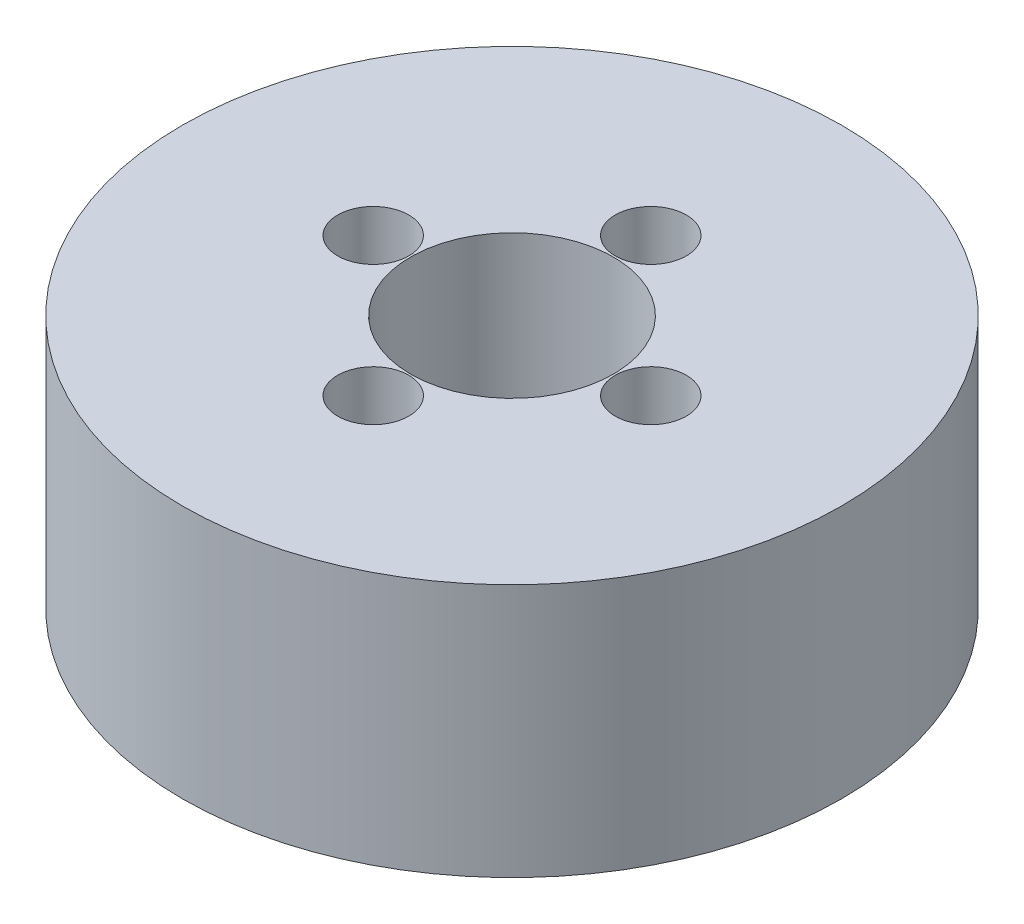
SolidWorks part; units mm, degrees
ref_plane "Front Plane" through (0, 0, 0) normal (0, 0, 1) x (1, 0, 0)
ref_plane "Top Plane" through (0, 0, 0) normal (0, 1, 0) x (1, 0, 0)
ref_plane "Right Plane" through (0, 0, 0) normal (1, 0, 0) x (0, 0, -1)
sketch "Sketch1" plane through (0, 0, 0) normal (0, 1, 0) x (1, 0, 0)
  circle A0 centre (0, 0) radius 32.5
  dimension "FLANGE_OD" = 65
extrude "Boss-Extrude1" add sketch "Sketch1" along normal blind 25
sketch "Sketch2" plane through (0, 0, 0) normal (0, 1, 0) x (1, 0, 0)
  circle A0 centre (0, 0) radius 10
  dimension "BORE_D" = 20
extrude "Cut-Extrude1" cut sketch "Sketch2" along normal through all
sketch "Sketch3" plane through (0, 25, 0) normal (0, 1, 0) x (1, 0, 0)
  circle A0 centre (0, 0) radius 13.6802 construction
  circle A1 centre (-13.6802, 0) radius 3.5024
  dimension "BOLT_D" = 7.0048
  dimension "BOLT_PCD" = 27.3604
extrude "Cut-Extrude2" cut sketch "Sketch3" against normal blind 22.9748
pattern_circular "CirPattern1" count 4 over 360 about axis through (0, 0, 0) along (0, 1, 0) of "Cut-Extrude2"
